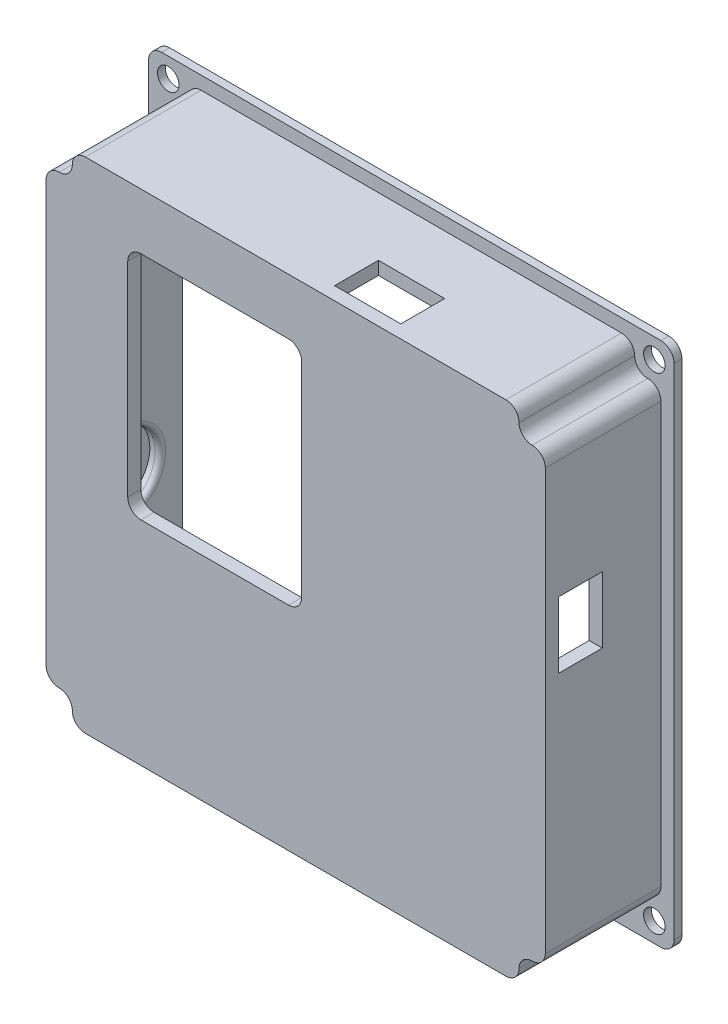
SolidWorks part; units mm, degrees
ref_plane "Alzado" through (0, 0, 0) normal (1, 0, 0) x (0, 1, 0)
ref_plane "Planta" through (0, 0, 0) normal (0, 0, 1) x (0, 1, 0)
ref_plane "Vista lateral" through (0, 0, 0) normal (0, 1, 0) x (-1, 0, 0)
sketch "Croquis1" plane through (0, 0, 0) normal (0, 0, 1) x (0, 1, 0)
  line L0 (-95, 85) -> (-85, 85)
  line L6 (-100, -100) -> (-100, 100)
  line L23 (-100, 100) -> (100, 100)
  line L25 (-100, 85) -> (-85, 85) construction
  line L26 (-100, 100) -> (0, 0) construction
  line L28 (-95, -85) -> (-95, 85)
  line L29 (-85, 95) -> (85, 95)
  line L31 (-85, 85) -> (-85, 100) construction
  line L32 (-95, 95) -> (0, 0) construction
  line L33 (-85, 85) -> (-85, 95)
  line L34 (-100, 0) -> (0, 0) construction
  line L35 (0, 0) -> (0, 100) construction
  line L36 (95, -85) -> (95, 85)
  line L37 (100, -100) -> (100, 100)
  line L38 (85, 85) -> (85, 95)
  line L39 (95, 85) -> (85, 85)
  line L40 (95, -85) -> (85, -85)
  line L41 (85, -85) -> (85, -95)
  line L42 (-85, -85) -> (-85, -95)
  line L43 (-85, -95) -> (85, -95)
  line L44 (-100, -100) -> (100, -100)
  line L45 (-95, -85) -> (-85, -85)
  circle A0 centre (-92.5, 92.5) radius 4.1
  circle A1 centre (92.5, 92.5) radius 4.1
  circle A2 centre (92.5, -92.5) radius 4.1
  circle A3 centre (-92.5, -92.5) radius 4.1
  point P0 (0, 0)
  point P1 (0, 0)
  point P3 (-92.5, 85)
  point P6 (-85, 92.5)
  point P27 (0, 95)
  point P30 (85, 92.5)
  point P31 (92.5, 85)
  point P33 (-95, 0)
  point P35 (100, 0)
  point P36 (95, 0)
  point P44 (92.5, -85)
  point P45 (85, -92.5)
  point P46 (0, -95)
  point P47 (-85, -92.5)
  point P48 (-92.5, -85)
  dimension "D6" = 8.2
  dimension "D1" = 100
  dimension "D2" = 100
  dimension "D3" = 5
  dimension "D4" = 5
  dimension "D5" = 15
extrude "Saliente-Extruir1" add sketch "Croquis1" along normal blind 3
sketch "Croquis2" plane through (0, 0, 3) normal (0, 0, 1) x (1, 0, 0)
  line L0 (-95, 85) -> (-95, -85) construction
  line L1 (-95, 85) -> (-95, -85)
  line L2 (-90, 80) -> (-90, -80)
  line L3 (95, 85) -> (95, -85)
  line L4 (90, 80) -> (90, -80)
  line L5 (85, 95) -> (85, 85)
  line L12 (-90, 80) -> (-90, -80)
  line L13 (-80, 80) -> (-90, 80)
  line L14 (-80, 90) -> (-80, 80)
  line L15 (85, 85) -> (95, 85)
  line L16 (80, 90) -> (80, 80)
  line L17 (80, 80) -> (90, 80)
  line L18 (80, -90) -> (-80, -90)
  line L19 (85, -95) -> (-85, -95)
  line L20 (-85, -95) -> (85, -95)
  line L21 (-85, -85) -> (-85, -95)
  line L22 (-95, -85) -> (-85, -85)
  line L23 (-95, 85) -> (-95, -85)
  line L24 (-85, 85) -> (-95, 85)
  line L25 (-85, 95) -> (-85, 85)
  line L26 (85, 95) -> (-85, 95)
  line L27 (85, 85) -> (85, 95)
  line L28 (95, 85) -> (85, 85)
  line L29 (95, -85) -> (95, 85)
  line L30 (85, -85) -> (95, -85)
  line L31 (85, -95) -> (85, -85)
  line L32 (-85, -95) -> (-85, -85)
  line L33 (-85, -85) -> (-95, -85)
  line L35 (-95, 85) -> (-95, -85)
  line L36 (-85, 85) -> (-95, 85)
  line L37 (-85, 95) -> (-85, 85)
  line L38 (85, 95) -> (-85, 95)
  line L39 (80, -80) -> (90, -80)
  line L40 (80, -90) -> (80, -80)
  line L41 (85, -85) -> (95, -85)
  line L43 (-80, -90) -> (-80, -80)
  line L44 (-80, -80) -> (-90, -80)
  line L45 (0, 0) -> (-95, 0) construction
  line L46 (0, 0) -> (0, 95) construction
  line L47 (80, 90) -> (-80, 90)
  line L48 (85, -95) -> (85, -85)
  point P2 (0, 90)
  point P8 (95, 0)
  point P14 (-90, 0)
  point P18 (90, 0)
  point P27 (0, -90)
  line M24 (85, -85) -> (85, -95)
  line M25 (85, -95) -> (-85, -95)
  line M26 (-85, -95) -> (-85, -85)
  line M27 (-85, -85) -> (-95, -85)
  line M28 (-95, -85) -> (-95, 85)
  line M29 (-95, 85) -> (-85, 85)
  line M30 (-85, 85) -> (-85, 95)
  line M31 (-85, 95) -> (85, 95)
  line M32 (85, 95) -> (85, 85)
  line M33 (85, 85) -> (95, 85)
  line M34 (95, 85) -> (95, -85)
  line M35 (95, -85) -> (85, -85)
  dimension "D1" = 5
  dimension "D2" = 5
  dimension "D3" = 5
  dimension "D4" = 5
  dimension "D6" = 0
extrude "Saliente-Extruir2" add sketch "Croquis2" along normal blind 39 and the other way up to surface (3 mm away) contours L47 L16 L17 L4 L39 L40 L18 L43 L44 L2 L13 L14 M24 M35 M34 M33 M32 M31 M30 M29 M28 M27 M26 M25 region at (-90, 82.313, 3) other way up to face at (-88.4, -92.5, 0)
sketch "Croquis3" plane through (0, 0, 42) normal (0, 0, 1) x (1, 0, 0)
  line L1 (-58.9212, 73.6862) -> (-2.717, 73.6862)
  line L2 (-63.9212, 68.6862) -> (-63.9212, -9.0525)
  line L3 (-58.9212, -14.0525) -> (-2.717, -14.0525)
  line L4 (2.283, 68.6862) -> (2.283, -9.0525)
  line L12 (85, -95) -> (85, -85)
  line L13 (85, -85) -> (95, -85)
  line L14 (95, -85) -> (95, 85)
  line L15 (95, 85) -> (85, 85)
  line L16 (85, 85) -> (85, 95)
  line L17 (85, 95) -> (-85, 95)
  line L18 (-85, 95) -> (-85, 85)
  line L19 (-85, 85) -> (-95, 85)
  line L20 (-95, 85) -> (-95, -85)
  line L21 (-95, -85) -> (-85, -85)
  line L22 (-85, -85) -> (-85, -95)
  line L23 (-85, -95) -> (85, -95)
  line L24 (85, -95) -> (85, -85)
  line L25 (85, -85) -> (95, -85)
  line L26 (95, -85) -> (95, 85)
  line L27 (95, 85) -> (85, 85)
  line L28 (85, 85) -> (85, 95)
  line L29 (85, 95) -> (-85, 95)
  line L30 (-85, 95) -> (-85, 85)
  line L31 (-85, 85) -> (-95, 85)
  line L32 (-95, 85) -> (-95, -85)
  line L33 (-95, -85) -> (-85, -85)
  line L34 (-85, -85) -> (-85, -95)
  line L35 (-85, -95) -> (85, -95)
  arc A0 (-63.9212, -9.0525) -> (-58.9212, -14.0525) centre (-58.9212, -9.0525) ccw
  arc A1 (-2.717, -14.0525) -> (2.283, -9.0525) centre (-2.717, -9.0525) ccw
  arc A2 (-2.717, 73.6862) -> (2.283, 68.6862) centre (-2.717, 68.6862) cw
  arc A3 (-58.9212, 73.6862) -> (-63.9212, 68.6862) centre (-58.9212, 68.6862) ccw
  dimension "D2" = 5
  dimension "D1" = 0
extrude "Saliente-Extruir3" add sketch "Croquis3" along normal blind 5
fillet "Redondeo1" radius 5 28 edges at (-95, -85, 25) (-85, -85, 25) (-85, -95, 25) (95, -85, 25) (85, -95, 25) (85, -85, 25) (95, 85, 25) (85, 85, 25) (85, 95, 25) (-85, 95, 25) (-85, 85, 25) (-95, 85, 25) (100, 100, 1.5) (-100, 100, 1.5) (-100, -100, 1.5) (100, -100, 1.5) (-90, 80, 21) (-80, 80, 21) (-80, 90, 21) (80, 90, 21) (80, 80, 21) (90, 80, 21) (90, -80, 21) (80, -80, 21) (80, -90, 21) (-80, -90, 21) (-80, -80, 21) (-90, -80, 21)
sketch "Croquis5" plane through (0, -100, 0) normal (0, -1, 0) x (1, 0, 0)
  line L0 (-95, 0) -> (95, 0) construction
  line L1 (-75.139, 0) -> (24.861, 0)
  line L2 (-75.139, 0) -> (-75.139, 42)
  line L3 (-75.139, 42) -> (24.861, 42)
  line L4 (24.861, 0) -> (24.861, 42)
  line L6 (-80, 47) -> (80, 47) construction
  dimension "D1" = 100
  dimension "D2" = 5
  dimension "D3" = 4.861
extrude "Cortar-Extruir2" cut sketch "Croquis5" against normal blind 12 contours L2 L3 L4 L1
sketch "Croquis6" plane through (0, -95, 0) normal (0, -1, 0) x (1, 0, 0)
  line L0 (24.861, 22.5) -> (80, 22.5) construction
  line L1 (24.861, 42) -> (24.861, 3) construction
  line L2 (80, 3) -> (80, 47) construction
  circle A2 centre (52.4305, 22.5) radius 10
  dimension "D1" = 20
extrude "Cortar-Extruir3" cut sketch "Croquis6" against normal blind 10
sketch "Croquis7" plane through (0, -90, 0) normal (0, 1, 0) x (-1, 0, 0)
  circle A0 centre (-52.4305, 22.5) radius 14
  dimension "D1" = 28
extrude "Cortar-Extruir4" cut sketch "Croquis7" against normal blind 4
fillet "Redondeo2" radius 2 1 edges at (38.4305, -90, 22.5)
sketch "Croquis8" plane through (-95, 0, 0) normal (-1, 0, 0) x (0, -1, 0)
  line L0 (27.1226, 42) -> (27.1226, 3) construction
  line L1 (-75, 42) -> (75, 42) construction
  line L2 (-95, 3) -> (95, 3) construction
  circle A0 centre (27.1226, 22.5) radius 10
  dimension "D1" = 20
extrude "Cortar-Extruir5" cut sketch "Croquis8" against normal blind 10
sketch "Croquis9" plane through (-90, 0, 0) normal (1, 0, 0) x (0, 1, 0)
  circle A0 centre (-27.1226, 22.5) radius 14
  dimension "D1" = 28
extrude "Cortar-Extruir6" cut sketch "Croquis9" against normal blind 4
fillet "Redondeo3" radius 2 1 edges at (-90, -13.1226, 22.5)
sketch "Croquis11" plane through (0, 95, 0) normal (0, -1, 0) x (1, 0, 0)
  line L0 (22.4, 42) -> (22.4, 3) construction
  line L3 (95, 3) -> (-95, 3) construction
  line L4 (9.8, 25.3) -> (35, 25.3)
  line L5 (9.8, 25.3) -> (9.8, 42)
  line L6 (9.8, 42) -> (35, 42)
  line L7 (35, 25.3) -> (35, 42)
  line L8 (9.8, 25.3) -> (35, 42) construction
  line L9 (9.8, 42) -> (35, 25.3) construction
  line L10 (75, 42) -> (-75, 42) construction
  line L11 (80, 47) -> (80, 3) construction
  point P6 (22.4, 33.65)
  dimension "D1" = 25.2
  dimension "D2" = 16.7
  dimension "D3" = 45
extrude "Cortar-Extruir8" cut sketch "Croquis11" along normal blind 5
sketch "Croquis12" plane through (95, 0, 0) normal (1, 0, 0) x (0, 1, 0)
  line L0 (22.4, 42) -> (22.4, 3) construction
  line L1 (9.8, 25.3) -> (35, 25.3)
  line L2 (9.8, 25.3) -> (9.8, 42)
  line L3 (9.8, 42) -> (35, 42)
  line L4 (35, 25.3) -> (35, 42)
  line L5 (9.8, 25.3) -> (35, 42) construction
  line L6 (9.8, 42) -> (35, 25.3) construction
  line L7 (-95, 3) -> (95, 3) construction
  line L8 (75, 42) -> (-75, 42) construction
  line L10 (80, 3) -> (80, 47) construction
  point P2 (22.4, 33.65)
  dimension "D1" = 16.7
  dimension "D2" = 25.2
  dimension "D3" = 45
extrude "Cortar-Extruir9" cut sketch "Croquis12" against normal blind 5
